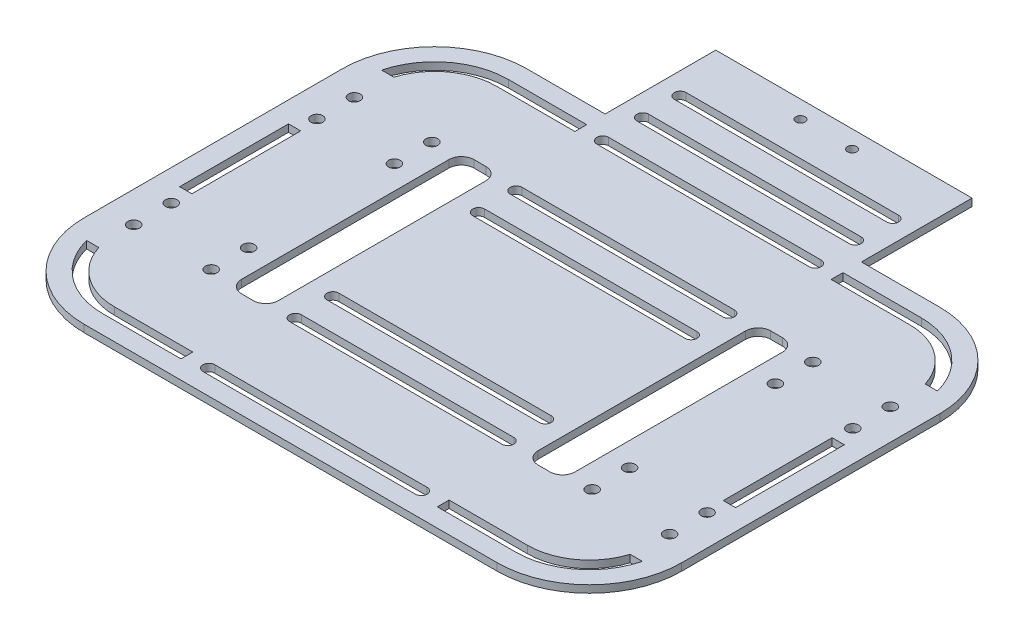
SolidWorks part; units mm, degrees
ref_plane "Front Plane" through (0, 0, 0) normal (0, 0, 1) x (1, 0, 0)
ref_plane "Top Plane" through (0, 0, 0) normal (0, 1, 0) x (1, 0, 0)
ref_plane "Right Plane" through (0, 0, 0) normal (1, 0, 0) x (0, 0, -1)
sketch "Sketch1" plane through (0, 0, 0) normal (0, 1, 0) x (1, 0, 0)
  line L0 (0, 0) -> (0, -79.375)
  line L1 (7.1438, -66.675) -> (-7.1437, -66.675)
  line L2 (50.8, 22.225) -> (76.2, 22.225)
  line L3 (-63.5, -47.625) -> (-50.8, -47.625)
  line L4 (-50.8, -47.625) -> (-50.8, 22.225)
  line L5 (63.5, -47.625) -> (50.8, -47.625)
  line L6 (50.8, -47.625) -> (50.8, 22.225)
  line L7 (-50.8, 22.225) -> (-76.2, 22.225)
  line L8 (0, 0) -> (-27.2811, 0)
  circle A0 centre (0, 0) radius 79.375
  circle A1 centre (-7.1437, -66.675) radius 1.5875
  circle A2 centre (7.1438, -66.675) radius 1.5875
  circle A3 centre (7.1438, 66.675) radius 1.5875
  circle A4 centre (-7.1437, 66.675) radius 1.5875
  point P7 (0, -66.675)
  dimension "D1" = 7.1437
  dimension "D3" = 50.8
  dimension "D6" = 3.175
  dimension "D2" = 12.7
  dimension "D4" = 69.85
  dimension "D5" = 47.625
extrude "Boss-Extrude5" add sketch "Sketch1" along normal blind 1.5875 contours A2 A0 L5 L6 L2 L7 L4 L3 A1 A3 region at (0, 0, -2.0947)
fillet "Fillet2" radius 2.54 1 edges at (-63.5, 0.7937, 47.625)
fillet "Fillet3" radius 2.54 1 edges at (63.5, 0.7937, 47.625)
fillet "Fillet4" radius 5.08 2 edges at (-76.2, 0.7937, -22.225) (76.2, 0.7937, -22.225)
sketch "Sketch2" plane through (0, 1.5875, 0) normal (0, 1, 0) x (1, 0, 0)
  line L0 (0, 0) -> (0, 79.375)
  line L1 (0, 0) -> (-67.0566, 0)
  line L2 (0, 0) -> (-61.0886, 27.6545)
  line L3 (0, 0) -> (-43.6778, 50.8806)
  line L4 (0, 0) -> (-63.2664, 22.225)
  line L5 (-50.8, 22.225) -> (-69.0955, 22.225) construction
  line L6 (0, 0) -> (0, 2.6153)
  line L7 (0, 0) -> (-39.0771, 54.4938)
  line L8 (0, 0) -> (-12.3858, 65.9028)
  line L9 (-62.5348, 28.3092) -> (-59.6424, 26.9998)
  line L10 (-43.6778, 50.8806) -> (-44.7118, 52.0852)
  line L11 (-43.6778, 50.8806) -> (-42.6438, 49.6761)
  line L12 (-39.0771, 54.4938) -> (-40.0022, 55.7839)
  line L13 (-39.0771, 54.4938) -> (-38.152, 53.2037)
  line L14 (-43.6778, 50.8806) -> (-42.6438, 49.6761)
  line L15 (-12.3858, 65.9028) -> (-12.0926, 64.3426)
  line L16 (-12.3858, 65.9028) -> (-12.679, 67.463)
  line L17 (61.5813, 22.225) -> (64.9466, 22.225)
  line L18 (50.8, 22.225) -> (69.0955, 22.225) construction
  line L19 (12.3858, 65.9028) -> (12.679, 67.463)
  line L20 (12.3858, 65.9028) -> (12.0926, 64.3426)
  line L21 (39.0771, 54.4938) -> (38.152, 53.2037)
  line L22 (43.6778, 50.8806) -> (42.6438, 49.6761)
  line L23 (39.0771, 54.4938) -> (40.0022, 55.7839)
  line L24 (43.6778, 50.8806) -> (42.6438, 49.6761)
  line L25 (43.6778, 50.8806) -> (44.7118, 52.0852)
  line L26 (62.5348, 28.3092) -> (59.6424, 26.9998)
  line L27 (-50.8, -41.2985) -> (-50.8, -43.7716)
  line L28 (-50.8, -47.625) -> (-50.8, 22.225) construction
  line L29 (50.8, -41.2985) -> (50.8, -46.1668)
  line L30 (50.8, -47.625) -> (50.8, 22.225) construction
  line L31 (39.0771, -54.4938) -> (40.0022, -55.7839)
  line L32 (39.0771, -54.4938) -> (38.152, -53.2037)
  line L33 (12.3858, -65.9028) -> (12.0926, -64.3426)
  line L34 (12.3858, -65.9028) -> (12.679, -67.463)
  line L35 (-12.3858, -65.9028) -> (-12.679, -67.463)
  line L36 (-12.3858, -65.9028) -> (-12.0926, -64.3426)
  line L37 (-39.0771, -54.4938) -> (-38.152, -53.2037)
  line L38 (-39.0771, -54.4938) -> (-40.0022, -55.7839)
  arc A0 (-63.2664, 22.225) -> (-50.8, -43.7716) centre (0, 0) ccw
  arc A1 (73.8199, 29.172) -> (-73.8199, 29.172) centre (0, 0) ccw construction
  circle A2 centre (-7.1437, 66.675) radius 2.3813
  circle A3 centre (7.1437, 66.675) radius 2.3813
  circle A4 centre (7.1437, -66.675) radius 2.3813
  circle A5 centre (-7.1437, -66.675) radius 2.3813
  arc A6 (12.679, -67.463) -> (40.0022, -55.7839) centre (0, 0) ccw
  arc A7 (-61.7686, 21.6988) -> (-50.8, -41.2985) centre (0, 0) ccw
  arc A8 (-44.7118, 52.0852) -> (-62.5348, 28.3092) centre (0, 0) ccw
  arc A9 (-42.6438, 49.6761) -> (-59.6424, 26.9998) centre (0, 0) ccw
  arc A10 (12.0926, 64.3426) -> (38.152, 53.2037) centre (0, 0) cw
  arc A11 (12.679, 67.463) -> (40.0022, 55.7839) centre (0, 0) cw
  arc A12 (42.6438, 49.6761) -> (59.6424, 26.9998) centre (0, 0) cw
  arc A13 (-12.679, 67.463) -> (-40.0022, 55.7839) centre (0, 0) ccw
  arc A14 (44.7118, 52.0852) -> (62.5348, 28.3092) centre (0, 0) cw
  arc A15 (-12.0926, 64.3426) -> (-38.152, 53.2037) centre (0, 0) ccw
  arc A16 (12.0926, -64.3426) -> (38.152, -53.2037) centre (0, 0) ccw
  arc A17 (-12.0926, -64.3426) -> (-38.152, -53.2037) centre (0, 0) cw
  arc A18 (50.8, -46.1668) -> (64.9466, 22.225) centre (0, 0) ccw
  arc A19 (50.8, -43.7716) -> (63.2664, 22.225) centre (0, 0) ccw
  arc A20 (50.8, -41.2985) -> (61.5813, 22.225) centre (0, 0) ccw
  arc A21 (-12.679, -67.463) -> (-40.0022, -55.7839) centre (0, 0) cw
  circle M13 centre (-7.1437, -66.675) radius 1.5875
  circle M14 centre (7.1438, -66.675) radius 1.5875
  circle M15 centre (7.1438, 66.675) radius 1.5875
  circle M16 centre (-7.1437, 66.675) radius 1.5875
  dimension "D2" = 4.7625
  dimension "D7" = 1.5875
  dimension "D8" = 3.175
  dimension "D1" = 5
  dimension "D3" = 25
  dimension "D4" = 5
  dimension "D5" = 25
extrude "Cut-Extrude1" cut sketch "Sketch2" against normal blind 2.54 contours A9 L3 L10 A8 L9 L2 | A15 L8 L16 A13 L12 L7 | A2 M16 | A3 M15 | A11 L19 L20 A10 L21 L23 | A14 L25 L22 A12 L26 | A21 L35 L36 A17 L37 L38 | A5 M13 | A4 M14 | A16 L33 L34 A6 L31 L32 region at (-53.2404, 1.5875, -39.9101) region at (-26.1525, 1.5875, -61.1833) region at (26.1525, 1.5875, -61.1833) region at (53.2404, 1.5875, -39.9101) region at (26.1525, 1.5875, 61.1833) region at (-26.1525, 1.5875, 61.1833) region at (-9.4576, 1.5875, -66.675) region at (4.8299, 1.5875, -66.675) region at (4.8299, 1.5875, 66.675) region at (-9.4576, 1.5875, 66.675)
sketch "Sketch3" plane through (0, 1.5875, 0) normal (0, 1, 0) x (1, 0, 0)
  line L0 (-50.8, 22.225) -> (-50.8, -47.625)
  line L1 (-50.8, -47.625) -> (-44.45, -47.625)
  line L2 (-50.8, 22.225) -> (-44.45, 22.225)
  line L3 (0, 0) -> (0, 32.9013)
  circle A0 centre (-44.45, -47.625) radius 1.5875
  circle A1 centre (-44.45, 22.225) radius 1.5875
  circle A2 centre (44.45, 22.225) radius 1.5875
  circle A3 centre (44.45, -47.625) radius 1.5875
  dimension "D2" = 3.175
  dimension "D4" = 3.175
  dimension "D1" = 6.35
  dimension "D3" = 6.35
extrude "Cut-Extrude2" cut sketch "Sketch3" against normal blind 2.54 contours A1 | A2 | A0 | A3 region at (-44.45, 1.5875, 46.0824) region at (-44.45, 1.5875, -23.7676) region at (44.45, 1.5875, -22.225) region at (44.45, 1.5875, 47.625)
sketch "Sketch4" plane through (0, 1.5875, 0) normal (0, 1, 0) x (1, 0, 0)
  line L0 (-44.45, -47.625) -> (-44.45, 22.225)
  line L1 (-44.45, 22.225) -> (-50.8, 22.225)
  line L2 (-50.8, -47.625) -> (-50.8, 22.225) construction
  line L3 (0, 0) -> (0, -67.5878)
  line L4 (44.45, -47.625) -> (44.45, 22.225)
  circle A0 centre (-44.45, 22.225) radius 1.5875
  circle A1 centre (-44.45, -12.7) radius 1.5875
  circle A2 centre (44.45, -12.7) radius 1.5875
  dimension "D2" = 3.175
  dimension "D1" = 69.85
extrude "Cut-Extrude3" cut sketch "Sketch4" against normal blind 2.54 contours L0 A1 | L0 A1 | A2 L4 | A2 L4 region at (-45.1238, 1.5875, 12.7) region at (-43.7762, 1.5875, 12.7) region at (43.7762, 1.5875, 12.7) region at (45.1238, 1.5875, 12.7)
sketch "Sketch5" plane through (0, 1.5875, 0) normal (0, 1, 0) x (1, 0, 0)
  line L0 (-50.8, -12.7) -> (-34.8, -12.7)
  line L1 (-50.8, -47.625) -> (-50.8, 22.225) construction
  line L2 (-50.8, 22.225) -> (-34.8, 22.225)
  line L3 (-34.8, 22.225) -> (-34.8, -12.7)
  line L4 (0, 0) -> (0, 64.5379)
  line L5 (-34.8, 22.225) -> (-19.8, 22.225)
  line L6 (-19.8, 22.225) -> (-19.8, -12.7)
  line L7 (-19.8, -12.7) -> (-34.8, -12.7)
  line L8 (19.8, -12.7) -> (34.8, -12.7)
  line L9 (19.8, 22.225) -> (19.8, -12.7)
  line L10 (34.8, 22.225) -> (19.8, 22.225)
  line L11 (34.8, 22.225) -> (34.8, -12.7)
  dimension "D1" = 16
  dimension "D2" = 16
extrude "Cut-Extrude4" cut sketch "Sketch5" against normal through all contours L7 L6 L5 L3 | L11 L10 L9 L8 region at (-27.3, 1.5875, -4.7625) region at (27.3, 1.5875, -4.7625)
fillet "Fillet5" radius 7.62 4 edges at (-19.8, 0.7937, 12.7) (-34.8, 0.7937, 12.7) (-19.8, 0.7937, -22.225) (-34.8, 0.7937, -22.225)
fillet "Fillet6" radius 7.62 4 edges at (34.8, 0.7937, 12.7) (34.8, 0.7937, -22.225) (19.8, 0.7937, -22.225) (19.8, 0.7937, 12.7)
sketch "Sketch6" plane through (0, 0, 0) normal (0, -1, 0) x (-1, 0, 0)
  circle A0 centre (0, 0) radius 79.375
extrude "Cut-Extrude5" cut sketch "Sketch6" against normal blind 0.5875
sketch "Sketch8" plane through (0, 1.5875, 0) normal (0, 1, 0) x (1, 0, 0)
  line L0 (-50.8, 22.225) -> (-50.8, 24.225)
  line L1 (-50.8, 24.225) -> (-80.2365, 24.225)
  line L2 (0, 0) -> (0, 19.3161)
  line L3 (0, 0) -> (-9.6505, 0)
  line L4 (50.8, 24.225) -> (80.2365, 24.225)
  line L5 (50.8, 22.225) -> (50.8, 24.225)
  line L6 (-50.8, -47.625) -> (-50.8, -49.625)
  line L7 (-50.8, -49.625) -> (-75.4506, -49.625)
  line L8 (50.8, -49.625) -> (75.4506, -49.625)
  line L9 (50.8, -47.625) -> (50.8, -49.625)
  line L10 (-50.8, -47.625) -> (-75.4506, -47.625)
  line L11 (-75.4506, -47.625) -> (-75.4506, -49.625)
  line L12 (50.8, -47.625) -> (75.4506, -47.625)
  line L13 (75.4506, -49.625) -> (75.4506, -47.625)
  line L14 (50.8, 22.225) -> (80.2365, 22.225)
  line L15 (80.2365, 22.225) -> (80.2365, 24.225)
  line L16 (-50.8, 22.225) -> (-80.2365, 22.225)
  line L17 (-80.2365, 22.225) -> (-80.2365, 24.225)
extrude "Cut-Extrude6" cut sketch "Sketch8" against normal blind 2.54 contours L10 L11 L7 L6 | L8 L13 L12 L9 | L14 L15 L4 L5 | L1 L17 L16 L0 region at (65.5183, 1.5875, -23.225) region at (-63.1253, 1.5875, 48.625) region at (63.1253, 1.5875, 48.625)
fillet "Fillet7" radius 2.54 4 edges at (-60.6806, 1.0875, 49.625) (60.6806, 1.0875, 49.625) (73.1353, 1.0875, -24.225) (-73.1353, 1.0875, -24.225)
sketch "Sketch11" plane through (0, 1.5875, 0) normal (0, 1, 0) x (1, 0, 0)
  line L1 (-11.0583, 60.7829) -> (11.2037, 60.7829)
  line L2 (-11.0583, 60.7829) -> (-11.0583, 72.1091)
  line L3 (-11.0583, 72.1091) -> (11.2037, 72.1091)
  line L4 (11.2037, 60.7829) -> (11.2037, 72.1091)
  line L5 (-11.0583, -61.658) -> (11.2037, -61.658)
  line L6 (-11.0583, -61.658) -> (-11.0583, -72.2032)
  line L7 (-11.0583, -72.2032) -> (11.2037, -72.2032)
  line L8 (11.2037, -61.658) -> (11.2037, -72.2032)
extrude "Boss-Extrude7" add sketch "Sketch11" against normal up to surface (1 mm away) up to face at (0, 0.5875, 5.2491)
sketch "Sketch12" plane through (0, 1.5875, 0) normal (0, 1, 0) x (1, 0, 0)
  line L0 (0, 0) -> (0, 79.375)
  line L1 (0, 0) -> (-6.75, 0)
  line L4 (0, 65.9028) -> (-6.75, 65.9028)
  line L5 (0, -65.9028) -> (-6.75, -65.9028)
  line L6 (-12.3858, -65.9028) -> (12.3858, -65.9028)
  line L7 (-12.0926, -64.3426) -> (-12.679, -67.463) construction
  line L8 (12.679, -67.463) -> (12.0926, -64.3426) construction
  arc A0 (73.8199, 29.172) -> (-73.8199, 29.172) centre (0, 0) ccw construction
  circle A1 centre (-6.75, 65.9028) radius 1.25
  circle A2 centre (6.75, 65.9028) radius 1.25
  circle A3 centre (6.75, -65.9028) radius 1.25
  circle A4 centre (-6.75, -65.9028) radius 1.25
  dimension "D1" = 2.5
  dimension "D2" = 13.5
extrude "Cut-Extrude7" cut sketch "Sketch12" against normal blind 2.54 contours A4 L6 | A4 L6 | L6 A3 | L6 A3 | A1 | A2 region at (-6.75, 1.5875, 66.4333) region at (-6.75, 1.5875, 65.3723) region at (6.75, 1.5875, 65.3723) region at (6.75, 1.5875, 66.4333) region at (-7.9646, 1.5875, -65.9028) region at (6.75, 1.5875, -65.9028)
sketch "Sketch14" plane through (0, 1.5875, 0) normal (0, 1, 0) x (1, 0, 0)
  circle A0 centre (-44.45, -12.7) radius 1.5875
  circle A2 centre (44.45, -12.7) radius 1.5875
  dimension "D1" = 3.175
extrude "Boss-Extrude8" add sketch "Sketch14" against normal up to surface (1 mm away) up to face at (-6.75, 0.5875, 64.6528)
sketch "Sketch15" plane through (0, 1.5875, 0) normal (0, 1, 0) x (1, 0, 0)
  line L0 (-44.45, 22.225) -> (-44.45, -1.0583)
  line L1 (-44.45, -1.0583) -> (-44.45, -24.3417)
  line L2 (0, 0) -> (0, 10.0728)
  line L3 (44.45, -1.0583) -> (44.45, -24.3417)
  circle A0 centre (-44.45, -1.0583) radius 1.5875
  circle A1 centre (-44.45, -24.3417) radius 1.5875
  circle A2 centre (44.45, -24.3417) radius 1.5875
  circle A3 centre (44.45, -1.0583) radius 1.5875
  dimension "D1" = 23.2833
  dimension "D2" = 3.175
  dimension "D3" = 23.2833
extrude "Cut-Extrude8" cut sketch "Sketch15" against normal blind 2.54 contours L1 A0 L0 | L0 A0 L1 | A1 | A2 | A3 region at (-43.7762, 1.5875, 1.0583) region at (-43.3592, 1.5875, 23.2509) region at (-45.1238, 1.5875, 1.0583) region at (45.5408, 1.5875, 23.2509) region at (43.3592, 1.5875, -0.0324)
sketch "Sketch16" plane through (0, 1.5875, 0) normal (0, 1, 0) x (1, 0, 0)
  line L0 (-44.45, -1.0583) -> (-51.5937, -1.0583)
  line L1 (-50.8, -49.625) -> (-56.413, -49.625) construction
  line L2 (-50.8, 24.225) -> (-51.5937, 24.225)
  line L3 (-50.8, 24.225) -> (-50.8, -49.625)
  line L4 (-50.8, -49.625) -> (-51.5937, -49.625)
  line L5 (-51.5937, 24.225) -> (-51.5937, -49.625)
  line L6 (0, 0) -> (0, 12.3631)
  line L7 (51.5937, 24.225) -> (51.5937, -49.625)
  line L8 (50.8, -49.625) -> (51.5937, -49.625)
  line L9 (50.8, 24.225) -> (50.8, -49.625)
  line L10 (50.8, 24.225) -> (51.5937, 24.225)
extrude "Boss-Extrude13" add sketch "Sketch16" against normal up to surface (1 mm away) contours L2 L5 L0 L3 | L0 L5 L4 L3 | L10 L9 L8 L7 region at (-51.1969, 1.5875, 25.3417) region at (-51.1969, 1.5875, -11.5833) region at (51.1969, 1.5875, 12.7) up to face at (44.45, 0.5875, 22.7542)
sketch "Sketch17" plane through (0, 1.5875, 0) normal (0, 1, 0) x (1, 0, 0)
  line L0 (0, 0) -> (0, 79.375)
  line L1 (0, 0) -> (-11.9199, 67.6013)
  line L2 (0, 0) -> (12.0176, 0)
  line L3 (0, 0) -> (-62.5348, 28.3092)
  line L4 (0, 0) -> (11.9199, 67.6013)
  line L5 (0, 0) -> (62.5348, 28.3092)
  line L6 (0, 0) -> (-40.0022, -55.7839)
  line L7 (0, 0) -> (11.9199, -67.6013)
  line L8 (0, 0) -> (-11.9199, -67.6013)
  line L9 (0, 0) -> (40.0022, -55.7839)
  arc A0 (73.8199, 29.172) -> (-73.8199, 29.172) centre (0, 0) ccw construction
  circle A1 centre (0, 0) radius 68.6441
  circle A2 centre (0, 0) radius 65.4691
  dimension "D1" = 10
extrude "Cut-Extrude10" cut sketch "Sketch17" against normal through all contours A2 L1 A1 L3 | A2 L5 A1 L4 | A2 L7 A1 L9 | A2 L6 A1 L8 region at (-40.5469, 1.5875, -52.2313) region at (12.2875, 1.5875, -65.9244) region at (-25.7975, 1.5875, 61.3039) region at (25.7975, 1.5875, 61.3039)
sketch "Sketch18" plane through (0, 1.5875, 0) normal (0, 1, 0) x (1, 0, 0)
  line L0 (0, 0) -> (0, 79.375)
  line L1 (0, 0) -> (-26.9517, 0)
  line L2 (0, 0) -> (-11.9199, 67.6013)
  line L3 (0, 0) -> (-34.3221, 59.4475)
  line L4 (0, 0) -> (-44.1236, 52.5844)
  line L5 (0, 0) -> (-59.4475, 34.3221)
  line L6 (-62.5348, 28.3092) -> (-59.6424, 26.9998)
  line L7 (0, 0) -> (11.9199, 67.6013)
  line L8 (0, 0) -> (34.3221, 59.4475)
  line L9 (0, 0) -> (44.1236, 52.5844)
  line L10 (0, 0) -> (59.4475, 34.3221)
  line L11 (0, 0) -> (44.1236, -52.5844)
  line L12 (0, 0) -> (-44.1236, -52.5844)
  line L13 (0, 0) -> (34.3221, -59.4475)
  line L14 (0, 0) -> (11.9199, -67.6013)
  line L15 (0, 0) -> (-11.9199, -67.6013)
  line L16 (0, 0) -> (-34.3221, -59.4475)
  line L17 (59.6424, 26.9998) -> (62.5348, 28.3092)
  line L18 (40.0022, -55.7839) -> (38.152, -53.2037)
  line L19 (-38.152, -53.2037) -> (-40.0022, -55.7839)
  arc A0 (73.8199, 29.172) -> (-73.8199, 29.172) centre (0, 0) ccw construction
  circle A1 centre (0, 0) radius 68.6441
  circle A2 centre (0, 0) radius 65.4691
  dimension "D1" = 20
  dimension "D2" = 10
  dimension "D3" = 20
extrude "Boss-Extrude16" add sketch "Sketch18" against normal up to surface (1 mm away) contours A2 L19 A1 L16 | A2 L13 A1 L18 | A2 L17 A1 L10 | A2 L9 A1 L8 | A2 L3 A1 L4 | A2 L5 A1 L6 region at (-38.4205, 1.5875, -54.8701) region at (-59.64, 1.5875, -30.6219) region at (38.4205, 1.5875, -54.8701) region at (59.64, 1.5875, -30.6219) region at (36.3389, 1.5875, 56.3393) region at (-36.3389, 1.5875, 56.3393) up to face at (25.6849, 0.5875, 61.0364)
sketch "Sketch19" plane through (0, 1.5875, 0) normal (0, 1, 0) x (1, 0, 0)
  line L0 (33.7, 150.1124) -> (33.7, 185.1124)
  line L1 (0, 79.375) -> (0, -79.375)
  line L2 (-51.5937, 24.225) -> (51.5937, 24.225)
  line L3 (-51.5937, 24.225) -> (-51.5937, -49.625)
  line L4 (-51.5937, -49.625) -> (51.5937, -49.625)
  line L5 (51.5937, 24.225) -> (51.5937, -49.625)
  line L6 (37.7, 90.1124) -> (149.7, 90.1124)
  line L7 (-172.4279, 149.4503) -> (-117.4279, 149.4503)
  line L8 (-172.4279, 149.4503) -> (-172.4279, 121.4503)
  line L9 (-172.4279, 121.4503) -> (-117.4279, 121.4503)
  line L10 (-117.4279, 149.4503) -> (-117.4279, 121.4503)
  line L11 (219.5866, 324.1917) -> (264.5866, 324.1917)
  line L12 (219.5866, 324.1917) -> (219.5866, 272.1917)
  line L13 (219.5866, 272.1917) -> (264.5866, 272.1917)
  line L14 (264.5866, 324.1917) -> (264.5866, 272.1917)
  line L15 (51.5937, -49.625) -> (11.5937, -49.625)
  line L16 (51.5937, -49.625) -> (51.5937, -14.625)
  line L17 (51.5937, -14.625) -> (11.5937, -14.625)
  line L18 (11.5937, -49.625) -> (11.5937, -14.625)
  line L19 (93.7, 90.1124) -> (93.7, 230.1124)
  line L21 (174.7, 115.1124) -> (153.7, 115.1124)
  line L22 (12.7, 185.1124) -> (33.7, 185.1124)
  line L23 (78.6997, 149.9601) -> (87.6997, 149.9296)
  line L24 (38.7, 167.1124) -> (38.7, 133.1124)
  line L25 (78.6427, 133.1124) -> (38.7, 133.1124)
  line L26 (78.7578, 167.1124) -> (78.6427, 133.1124)
  line L27 (78.7578, 167.1124) -> (38.7, 167.1124)
  line L28 (33.7, 150.1124) -> (12.7, 150.1124)
  line L29 (242.0866, 324.1917) -> (242.0866, 272.1917)
  line L30 (37.7, 210.1124) -> (58.953, 210.1124)
  line L31 (290.0855, 218.8978) -> (400.0855, 218.8978)
  line L32 (290.0855, 218.8978) -> (290.0855, 165.8978)
  line L33 (290.0855, 165.8978) -> (400.0855, 165.8978)
  line L34 (400.0855, 218.8978) -> (400.0855, 165.8978)
  line L35 (-58.953, -52.165) -> (-58.953, 24.225)
  line L36 (-51.5937, 24.225) -> (-71.5774, 24.225) construction
  line L37 (-58.953, 24.225) -> (-51.5937, 24.225)
  line L38 (-58.953, -52.165) -> (-51.5937, -49.625)
  line L39 (58.953, -52.165) -> (51.5937, -49.625)
  line L40 (58.953, 24.225) -> (51.5937, 24.225)
  line L41 (58.953, -52.165) -> (58.953, 24.225)
  line L42 (51.5937, 24.225) -> (51.5937, -49.625)
  line L43 (12.7, 120.1124) -> (12.7, 180.1124)
  line L44 (12.7, 180.1124) -> (22.7, 180.1124)
  line L45 (22.7, 180.1124) -> (22.7, 120.1124)
  line L46 (22.7, 120.1124) -> (12.7, 120.1124)
  line L47 (38.7, 150.1124) -> (33.7, 150.1124)
  line L49 (128.447, 230.1124) -> (128.447, 210.1124)
  line L50 (153.7, 150.1124) -> (153.7, 115.1124)
  line L51 (148.7, 150.1124) -> (153.7, 150.1124)
  line L52 (164.7, 120.1124) -> (174.7, 120.1124)
  line L53 (164.7, 180.1124) -> (164.7, 120.1124)
  line L54 (174.7, 180.1124) -> (164.7, 180.1124)
  line L55 (174.7, 120.1124) -> (174.7, 180.1124)
  line L56 (149.7, 210.1124) -> (128.447, 210.1124)
  line L57 (33.7, 150.1124) -> (33.7, 115.1124)
  line L58 (153.7, 150.1124) -> (174.7, 150.1124)
  line L59 (108.6422, 167.1124) -> (148.7, 167.1124)
  line L60 (108.6422, 167.1124) -> (108.7573, 133.1124)
  line L61 (108.7573, 133.1124) -> (148.7, 133.1124)
  line L62 (58.953, 230.1124) -> (58.953, 210.1124)
  line L63 (174.7, 185.1124) -> (153.7, 185.1124)
  line L64 (148.7, 167.1124) -> (148.7, 133.1124)
  line L65 (108.7003, 149.9601) -> (99.7003, 149.9296)
  line L66 (153.7, 150.1124) -> (153.7, 185.1124)
  line L67 (-325.826, 349.5435) -> (-272.826, 349.5435)
  line L68 (-325.826, 349.5435) -> (-325.826, 239.5435)
  line L69 (-325.826, 239.5435) -> (-272.826, 239.5435)
  line L70 (-272.826, 349.5435) -> (-272.826, 239.5435)
  line L71 (-215.9733, 300.1641) -> (-187.9733, 300.1641)
  line L72 (-215.9733, 300.1641) -> (-215.9733, 245.1641)
  line L73 (-215.9733, 245.1641) -> (-187.9733, 245.1641)
  line L74 (-187.9733, 300.1641) -> (-187.9733, 245.1641)
  line L75 (12.7, 115.1124) -> (33.7, 115.1124)
  line L76 (153.7, 180.1124) -> (153.7, 150.1124)
  line L78 (58.953, 230.1124) -> (58.953, 240.1124)
  line L79 (58.953, 240.1124) -> (128.447, 240.1124)
  line L80 (128.447, 230.1124) -> (128.447, 240.1124)
  arc A0 (73.8199, 29.172) -> (-73.8199, 29.172) centre (0, 0) ccw construction
  arc A1 (-58.2779, -53.8895) -> (58.2779, -53.8895) centre (0, 0) ccw construction
  arc A2 (-56.413, -49.625) -> (-58.2779, -53.8895) centre (-56.413, -52.165) ccw construction
  circle A3 centre (100.706, 94.8953) radius 1.25
  circle A4 centre (86.694, 235.3295) radius 1.25
  circle A5 centre (86.694, 94.8953) radius 1.25
  circle A6 centre (100.706, 235.3295) radius 1.25
  arc A7 (12.7, 115.1124) -> (37.7, 90.1124) centre (37.7, 115.1124) ccw
  arc A8 (174.7, 115.1124) -> (149.7, 90.1124) centre (149.7, 115.1124) cw
  arc A9 (12.7, 185.1124) -> (37.7, 210.1124) centre (37.7, 185.1124) cw
  arc A10 (174.7, 185.1124) -> (149.7, 210.1124) centre (149.7, 185.1124) ccw
  dimension "D15" = 55
  dimension "D1" = 103.1875
  dimension "D3" = 158.75
  dimension "D4" = 28
  dimension "D5" = 55
  dimension "D6" = 150
  dimension "D7" = 162
  dimension "D8" = 40
  dimension "D9" = 35
  dimension "D11" = 110
  dimension "D12" = 110
  dimension "D13" = 53
  dimension "D16" = 28
  dimension "D17" = 53
  dimension "D18" = 45
  dimension "D19" = 52
  dimension "D20" = 29.75
extrude "Boss-Extrude20" add sketch "Sketch19" along normal blind 2 separate body contours L63 A10 L56 L49 L80 L79 L78 L62 L30 A9 L22 L0 L24 L27 L26 L25 L57 L75 A7 L6 A8 L21 L50 L64 L61 L60 L59 L66 A4 A3 A5 | L26 L27 L24 L25 | L64 L59 L60 L61 region at (58.7001, 1.5875, -150.1206) region at (128.6999, 1.5875, -150.1206) region at (35.9078, 1.5875, -167.6124)
sketch "Sketch20" plane through (0, 3.5875, 0) normal (0, 1, 0) x (1, 0, 0)
  line L0 (33.7, 185.1124) -> (33.7, 180.0324)
  line L1 (33.7, 115.1124) -> (33.7, 185.1124) construction
  line L2 (42.05, 180.0324) -> (33.7, 180.0324)
  line L3 (33.7, 180.0324) -> (33.7, 175.0324)
  line L4 (33.7, 150.1124) -> (44.1466, 150.1124)
  line L5 (93.7, 240.1124) -> (93.7, 224.3413)
  line L6 (58.953, 240.1124) -> (128.447, 240.1124) construction
  circle A0 centre (42.05, 180.0324) radius 1.5875
  circle A1 centre (42.05, 169.8724) radius 1.5875
  circle A2 centre (42.05, 130.3524) radius 1.5875
  circle A3 centre (42.05, 120.1924) radius 1.5875
  circle A4 centre (145.35, 120.1924) radius 1.5875
  circle A5 centre (145.35, 130.3524) radius 1.5875
  circle A6 centre (145.35, 169.8724) radius 1.5875
  circle A7 centre (145.35, 180.0324) radius 1.5875
  dimension "D3" = 3.175
  dimension "D5" = 3.175
  dimension "D1" = 5.08
  dimension "D2" = 5
  dimension "D4" = 10.16
  dimension "D6" = 8.35
extrude "Cut-Extrude13" cut sketch "Sketch20" against normal blind 2 contours A0 | A1 | A2 | A3 | A4 | A5 | A6 | A7 region at (42.05, 3.5875, -178.4898) region at (42.05, 3.5875, -169.8724) region at (42.05, 3.5875, -130.3524) region at (42.05, 3.5875, -120.1924) region at (145.35, 3.5875, -120.1924) region at (145.35, 3.5875, -130.3524) region at (145.35, 3.5875, -169.8724) region at (145.35, 3.5875, -180.0324)
sketch "Sketch23" plane through (0, 3.5875, 0) normal (0, 1, 0) x (1, 0, 0)
  line L0 (64.903, 181.6324) -> (122.497, 181.6324)
  line L1 (122.497, 178.4324) -> (64.903, 178.4324)
  line L2 (37.7, 205.1124) -> (58.953, 205.1124)
  line L3 (122.497, 226.1324) -> (64.903, 226.1324)
  line L4 (37.7, 201.9124) -> (58.953, 201.9124)
  line L5 (122.497, 222.9324) -> (64.903, 222.9324)
  line L6 (122.497, 171.4724) -> (64.903, 171.4724)
  line L7 (64.903, 168.2724) -> (122.497, 168.2724)
  line L8 (169.0649, 190.1124) -> (165.7387, 190.1124)
  line L9 (93.7, 230.3124) -> (93.7, 236.6657)
  line L10 (58.953, 205.1124) -> (58.953, 201.9124)
  line L11 (-100.9547, 278.8038) -> (-40.9547, 278.8038)
  line L12 (-100.9547, 278.8038) -> (-100.9547, 248.8038)
  line L13 (-100.9547, 248.8038) -> (-40.9547, 248.8038)
  line L14 (-40.9547, 278.8038) -> (-40.9547, 248.8038)
  line L15 (122.497, 215.9724) -> (64.903, 215.9724)
  line L16 (-24.4507, 290.9638) -> (-63.4507, 290.9638)
  line L17 (-24.4507, 287.7638) -> (-63.4507, 287.7638)
  line L18 (-63.4507, 246.4638) -> (-24.4507, 246.4638)
  line L19 (-63.4507, 244.8638) -> (-24.4507, 244.8638)
  line L20 (-65.0507, 289.3638) -> (-65.0507, 244.8638)
  line L21 (-24.4507, 243.2638) -> (-63.4507, 243.2638)
  line L22 (-22.8507, 244.8638) -> (-22.8507, 289.3638)
  line L23 (122.497, 212.7724) -> (64.903, 212.7724)
  line L24 (18.3351, 190.1124) -> (21.6613, 190.1124)
  line L25 (12.7, 185.1124) -> (33.7, 185.1124) construction
  line L26 (64.903, 131.9524) -> (122.497, 131.9524)
  line L27 (122.497, 128.7524) -> (64.903, 128.7524)
  line L28 (122.497, 121.7924) -> (64.903, 121.7924)
  line L29 (64.903, 118.5924) -> (122.497, 118.5924)
  line L30 (128.447, 205.1124) -> (128.447, 201.9124)
  line L33 (64.903, 205.1124) -> (122.497, 205.1124)
  line L34 (64.903, 201.9124) -> (122.497, 201.9124)
  line L35 (128.447, 205.1124) -> (149.7, 205.1124)
  line L36 (128.447, 201.9124) -> (149.7, 201.9124)
  line L37 (33.7, 150.1124) -> (40.3143, 150.1124)
  line L38 (33.7, 115.1124) -> (33.7, 185.1124) construction
  line L39 (18.3351, 110.1124) -> (21.6613, 110.1124)
  line L40 (58.953, 95.1124) -> (58.953, 98.3124)
  line L41 (37.7, 98.3124) -> (58.953, 98.3124)
  line L42 (37.7, 95.1124) -> (58.953, 95.1124)
  line L43 (149.7, 95.1124) -> (128.447, 95.1124)
  line L44 (149.7, 98.3124) -> (128.447, 98.3124)
  line L45 (128.447, 95.1124) -> (128.447, 98.3124)
  line L46 (169.0649, 110.1124) -> (165.7387, 110.1124)
  line L47 (51.8765, 181.6324) -> (55.0765, 181.6324)
  line L48 (-34.8, 14.605) -> (-19.8, 14.605)
  line L49 (-34.8, 14.605) -> (-34.8, -5.08)
  line L50 (-34.8, -5.08) -> (-19.8, -5.08)
  line L51 (-19.8, 14.605) -> (-19.8, -5.08)
  line L52 (58.4765, 178.2324) -> (58.4765, 121.9924)
  line L53 (53.4765, 181.6324) -> (53.4765, 210.1124)
  line L54 (58.4765, 121.9924) -> (58.8603, 122.0299)
  line L55 (37.7, 210.1124) -> (58.953, 210.1124) construction
  line L56 (58.953, 210.1124) -> (58.953, 240.1124) construction
  line L57 (55.0765, 118.5924) -> (51.8765, 118.5924)
  line L58 (51.8765, 118.5924) -> (51.3797, 118.9575)
  line L59 (48.4765, 121.9924) -> (48.4765, 178.2324)
  line L60 (138.9235, 121.9924) -> (138.9235, 178.2324)
  line L61 (135.5235, 118.5924) -> (136.0203, 118.9575)
  line L62 (132.3235, 118.5924) -> (135.5235, 118.5924)
  line L63 (128.9235, 121.9924) -> (128.5397, 122.0299)
  line L64 (128.9235, 178.2324) -> (128.9235, 121.9924)
  line L65 (135.5235, 181.6324) -> (132.3235, 181.6324)
  arc A0 (-63.4507, 290.9638) -> (-63.4507, 287.7638) centre (-63.4507, 289.3638) ccw
  arc A1 (64.903, 226.1324) -> (64.903, 222.9324) centre (64.903, 224.5324) ccw
  arc A2 (122.497, 226.1324) -> (122.497, 222.9324) centre (122.497, 224.5324) cw
  arc A3 (64.903, 181.6324) -> (64.903, 178.4324) centre (64.903, 180.0324) ccw
  arc A4 (122.497, 181.6324) -> (122.497, 178.4324) centre (122.497, 180.0324) cw
  arc A5 (-24.4507, 290.9638) -> (-24.4507, 287.7638) centre (-24.4507, 289.3638) cw
  arc A6 (-63.4507, 246.4638) -> (-63.4507, 243.2638) centre (-63.4507, 244.8638) ccw
  arc A7 (-24.4507, 243.2638) -> (-24.4507, 246.4638) centre (-24.4507, 244.8638) ccw
  arc A8 (12.7, 185.1124) -> (37.7, 210.1124) centre (37.7, 185.1124) cw
  arc A9 (37.7, 205.1124) -> (18.3351, 190.1124) centre (37.7, 185.1124) ccw
  arc A10 (37.7, 201.9124) -> (21.6613, 190.1124) centre (37.7, 185.1124) ccw
  arc A11 (122.497, 168.2724) -> (122.497, 171.4724) centre (122.497, 169.8724) ccw
  arc A12 (64.903, 168.2724) -> (64.903, 171.4724) centre (64.903, 169.8724) cw
  arc A13 (149.7, 201.9124) -> (165.7387, 190.1124) centre (149.7, 185.1124) cw
  arc A14 (149.7, 205.1124) -> (169.0649, 190.1124) centre (149.7, 185.1124) cw
  arc A15 (64.903, 215.9724) -> (64.903, 212.7724) centre (64.903, 214.3724) ccw
  arc A16 (122.497, 215.9724) -> (122.497, 212.7724) centre (122.497, 214.3724) cw
  arc A17 (64.903, 131.9524) -> (64.903, 128.7524) centre (64.903, 130.3524) ccw
  arc A18 (122.497, 131.9524) -> (122.497, 128.7524) centre (122.497, 130.3524) cw
  arc A19 (122.497, 118.5924) -> (122.497, 121.7924) centre (122.497, 120.1924) ccw
  arc A20 (64.903, 118.5924) -> (64.903, 121.7924) centre (64.903, 120.1924) cw
  arc A21 (37.7, 98.3124) -> (21.6613, 110.1124) centre (37.7, 115.1124) cw
  arc A22 (37.7, 95.1124) -> (18.3351, 110.1124) centre (37.7, 115.1124) cw
  arc A23 (149.7, 95.1124) -> (169.0649, 110.1124) centre (149.7, 115.1124) ccw
  arc A24 (149.7, 98.3124) -> (165.7387, 110.1124) centre (149.7, 115.1124) ccw
  arc A25 (51.8765, 181.6324) -> (48.4765, 178.2324) centre (51.8765, 178.2324) ccw
  arc A26 (55.0765, 118.5924) -> (58.4765, 121.9924) centre (55.0765, 121.9924) ccw
  arc A27 (55.0765, 181.6324) -> (58.4765, 178.2324) centre (55.0765, 178.2324) cw
  arc A28 (51.8765, 118.5924) -> (48.4765, 121.9924) centre (51.8765, 121.9924) cw
  arc A29 (135.5235, 118.5924) -> (138.9235, 121.9924) centre (135.5235, 121.9924) ccw
  arc A30 (132.3235, 181.6324) -> (128.9235, 178.2324) centre (132.3235, 178.2324) ccw
  arc A31 (132.3235, 118.5924) -> (128.9235, 121.9924) centre (132.3235, 121.9924) cw
  arc A32 (135.5235, 181.6324) -> (138.9235, 178.2324) centre (135.5235, 178.2324) cw
  arc A33 (64.903, 205.1124) -> (64.903, 201.9124) centre (64.903, 203.5124) ccw
  arc A34 (122.497, 201.9124) -> (122.497, 205.1124) centre (122.497, 203.5124) ccw
  point P0 (93.7, 205.1124)
  point P52 (93.7, 201.9124)
  dimension "D3" = 3.2
  dimension "D1" = 30
  dimension "D6" = 5
  dimension "D4" = 5
  dimension "D2" = 60
  dimension "D5" = 5
  dimension "D7" = 15
  dimension "D8" = 1.6
  dimension "D9" = 5.4765
extrude "Cut-Extrude18" cut sketch "Sketch23" against normal blind 2 contours A10 L4 L53 L2 A9 L24 | L53 L4 L10 L2 | L34 A34 L33 A33 | A16 L15 A15 L23 | A2 L3 A1 L5 | A14 L35 L30 L36 A13 L8 | A28 L57 A26 L52 A27 L47 A25 L59 | A12 L7 A11 L6 | A4 L0 A3 L1 | A32 L65 A30 L64 A31 L62 A29 L60 | A22 L42 L40 L41 A21 L39 | A24 L44 L45 L43 A23 L46 | A20 L29 A19 L28 | A18 L26 A17 L27 | L34 A34 L33 A33 region at (93.7, 3.5875, -180.0324) region at (53.4765, 3.5875, -150.1124) region at (45.5883, 3.5875, -204.7303) region at (56.2148, 3.5875, -203.5124) region at (93.7, 3.5875, -224.5324) region at (93.7, 3.5875, -169.8724) region at (167.4018, 3.5875, -190.5454) region at (93.7, 3.5875, -214.3724) region at (93.7, 3.5875, -130.3524) region at (93.7, 3.5875, -120.1924) region at (93.7, 3.5875, -203.5124) region at (19.9982, 3.5875, -109.6794) region at (139.0735, 3.5875, -95.5454) region at (133.9235, 3.5875, -150.1124)
sketch "Sketch24" plane through (0, 3.5875, 0) normal (0, 1, 0) x (1, 0, 0)
  circle A0 centre (0, 0) radius 79.375
extrude "Cut-Extrude20" cut sketch "Sketch24" against normal through all
sketch "Sketch25" plane through (0, 3.5875, 0) normal (0, 1, 0) x (1, 0, 0)
  line L0 (18.3351, 190.1124) -> (18.3351, 110.1124)
  line L1 (33.7, 185.1124) -> (12.7, 185.1124)
  line L2 (33.7, 185.1124) -> (33.7, 115.1124)
  line L3 (33.7, 115.1124) -> (12.7, 115.1124)
  line L4 (12.7, 185.1124) -> (12.7, 115.1124)
  line L5 (19.9982, 190.1124) -> (42.05, 190.1124)
  line L6 (21.6613, 190.1124) -> (21.6613, 110.1124)
  line L7 (18.3351, 190.1124) -> (21.6613, 190.1124) construction
  line L8 (31.0241, 190.1124) -> (31.0241, 151.1684)
  line L9 (19.9982, 169.8724) -> (19.9982, 164.8724)
  line L10 (19.9982, 130.3524) -> (19.9982, 135.3524)
  line L11 (18.3351, 164.8724) -> (21.6613, 164.8724)
  line L12 (21.6613, 135.3524) -> (18.3351, 135.3524)
  line L13 (93.7, 240.1124) -> (93.7, 234.3105)
  line L14 (58.953, 240.1124) -> (128.447, 240.1124) construction
  line L15 (165.7387, 135.3524) -> (169.0649, 135.3524)
  line L16 (169.0649, 164.8724) -> (165.7387, 164.8724)
  line L17 (167.4018, 130.3524) -> (167.4018, 135.3524)
  line L18 (167.4018, 169.8724) -> (167.4018, 164.8724)
  line L19 (174.7, 185.1124) -> (174.7, 115.1124)
  line L20 (153.7, 115.1124) -> (174.7, 115.1124)
  line L21 (153.7, 185.1124) -> (153.7, 115.1124)
  line L22 (153.7, 185.1124) -> (174.7, 185.1124)
  line L23 (165.7387, 164.8724) -> (165.7387, 135.3524)
  line L24 (169.0649, 135.3524) -> (169.0649, 164.8724)
  circle A0 centre (42.05, 180.0324) radius 1.5875
  circle A1 centre (42.05, 169.8724) radius 1.5875
  circle A2 centre (42.05, 130.3524) radius 1.5875
  circle A3 centre (42.05, 120.1924) radius 1.5875
  circle A4 centre (19.9982, 130.3524) radius 1.5875
  circle A5 centre (19.9982, 169.8724) radius 1.5875
  circle A6 centre (19.9982, 180.0324) radius 1.5875
  circle A7 centre (19.9982, 120.1924) radius 1.5875
  circle A8 centre (167.4018, 120.1924) radius 1.5875
  circle A9 centre (167.4018, 180.0324) radius 1.5875
  circle A10 centre (167.4018, 169.8724) radius 1.5875
  circle A11 centre (167.4018, 130.3524) radius 1.5875
  dimension "D1" = 5
  dimension "D2" = 5
extrude "Boss-Extrude22" add sketch "Sketch25" against normal blind 2 contours L1 L4 L3 L0 | A5 L11 L6 L1 L0 A6 | L1 L6 L3 L2 | A4 L12 L0 L3 L6 A7 | L22 L21 L20 L19 A11 L15 L23 L16 A10 L24 A9 A8 region at (15.5175, 3.5875, -150.1124) region at (19.9982, 3.5875, -175.0047) region at (19.9982, 3.5875, -125.2201) region at (27.6807, 3.5875, -150.1124) region at (163.8898, 3.5875, -150.1124)
sketch "Sketch26" plane through (0, 3.5875, 0) normal (0, 1, 0) x (1, 0, 0)
  circle A2 centre (167.4018, 180.0324) radius 1.5875
  circle A3 centre (167.4018, 169.8724) radius 1.5875
  circle A4 centre (167.4018, 130.3524) radius 1.5875
  circle A5 centre (167.4018, 120.1924) radius 1.5875
  circle A6 centre (19.9982, 120.1924) radius 1.5875
  circle A7 centre (19.9982, 130.3524) radius 1.5875
  circle A8 centre (19.9982, 169.8724) radius 1.5875
  circle A9 centre (19.9982, 180.0324) radius 1.5875
extrude "Boss-Extrude23" add sketch "Sketch26" against normal blind 2
sketch "Sketch27" plane through (0, 3.5875, 0) normal (0, 1, 0) x (1, 0, 0)
  line L0 (42.05, 180.0324) -> (38.7646, 180.0324)
  line L1 (12.7, 180.0324) -> (21.05, 180.0324)
  line L2 (12.7, 185.1124) -> (12.7, 115.1124) construction
  line L3 (42.05, 169.8724) -> (21.05, 169.8724)
  line L4 (18.3351, 150.1124) -> (21.6613, 150.1124)
  line L5 (18.3351, 164.8724) -> (18.3351, 135.3524) construction
  line L6 (21.6613, 164.8724) -> (21.6613, 135.3524) construction
  line L7 (93.7, 240.1124) -> (93.7, 233.106)
  line L8 (58.953, 240.1124) -> (128.447, 240.1124) construction
  circle A0 centre (21.05, 180.0324) radius 1.5875
  circle A2 centre (21.05, 169.8724) radius 1.5875
  circle A3 centre (21.05, 130.3524) radius 1.5875
  circle A4 centre (21.05, 120.1924) radius 1.5875
  circle A5 centre (21.05, 180.0324) radius 1.5875
  circle A6 centre (21.05, 169.8724) radius 1.5875
  circle A7 centre (21.05, 130.3524) radius 1.5875
  circle A8 centre (21.05, 120.1924) radius 1.5875
  circle A9 centre (166.35, 120.1924) radius 1.5875
  circle A10 centre (166.35, 130.3524) radius 1.5875
  circle A11 centre (166.35, 169.8724) radius 1.5875
  circle A12 centre (166.35, 180.0324) radius 1.5875
  circle A13 centre (166.35, 120.1924) radius 1.5875
  circle A14 centre (166.35, 130.3524) radius 1.5875
  circle A15 centre (166.35, 169.8724) radius 1.5875
  circle A16 centre (166.35, 180.0324) radius 1.5875
  dimension "D1" = 8.35
  dimension "D2" = 3.175
  dimension "D3" = 3.175
extrude "Cut-Extrude22" cut sketch "Sketch27" against normal blind 2 contours A0 | A2 | A3 | A4 | A12 | A11 | A10 | A9 region at (21.05, 3.5875, -178.4898)
sketch "Sketch28" plane through (0, 3.5875, 0) normal (0, 1, 0) x (1, 0, 0)
  line L1 (76.5159, 107.3899) -> (112.9956, 107.3899)
  line L2 (76.5159, 107.3899) -> (76.5159, 91.5876)
  line L3 (76.5159, 91.5876) -> (112.9956, 91.5876)
  line L4 (112.9956, 107.3899) -> (112.9956, 91.5876)
extrude "Boss-Extrude24" add sketch "Sketch28" against normal up to surface (2 mm away) up to face at (166.35, 1.5875, -118.6049)
sketch "Sketch29" plane through (0, 3.5875, 0) normal (0, 1, 0) x (1, 0, 0)
  line L0 (12.7, 150.1124) -> (31.1455, 150.1124)
  line L1 (64.903, 205.1124) -> (122.497, 205.1124)
  line L2 (12.7, 185.1124) -> (12.7, 115.1124) construction
  line L3 (64.903, 201.9124) -> (122.497, 201.9124)
  line L4 (64.903, 98.3124) -> (122.497, 98.3124)
  line L5 (64.903, 95.1124) -> (122.497, 95.1124)
  arc A0 (122.497, 201.9124) -> (122.497, 205.1124) centre (122.497, 203.5124) ccw construction
  arc A1 (122.497, 201.9124) -> (122.497, 205.1124) centre (122.497, 203.5124) ccw
  arc A2 (64.903, 205.1124) -> (64.903, 201.9124) centre (64.903, 203.5124) ccw
  arc A3 (64.903, 95.1124) -> (64.903, 98.3124) centre (64.903, 96.7124) cw
  arc A4 (122.497, 98.3124) -> (122.497, 95.1124) centre (122.497, 96.7124) cw
extrude "Cut-Extrude23" cut sketch "Sketch29" against normal blind 10 contours A4 L4 A3 L5 region at (93.7, 3.5875, -96.7124)
